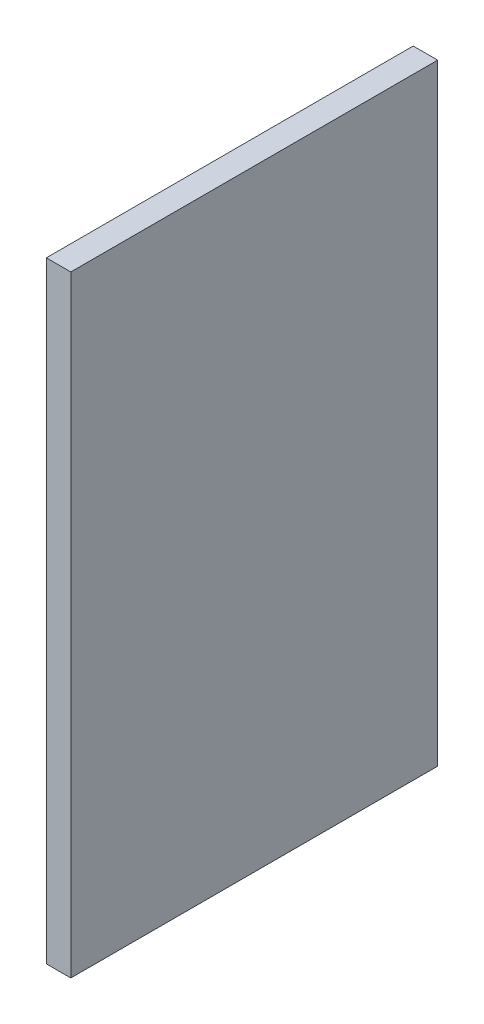
SolidWorks part; units mm, degrees
ref_plane "前视基准面" through (0, 0, 0) normal (0, 0, 1) x (1, 0, 0)
ref_plane "上视基准面" through (0, 0, 0) normal (0, 1, 0) x (1, 0, 0)
ref_plane "右视基准面" through (0, 0, 0) normal (1, 0, 0) x (0, 0, -1)
other "Configuration Table"
sketch "草图1" plane through (0, 0, 0) normal (0, 1, 0) x (1, 0, 0)
  line L1 (-110.8, -38) -> (-110, -38)
  line L2 (-110.8, -38) -> (-110.8, -26)
  line L3 (-110.8, -26) -> (-110, -26)
  line L4 (-110, -38) -> (-110, -26)
extrude "Mating_patch_20x12x0p8" add sketch "草图1" along normal blind 10 and the other way blind 10
